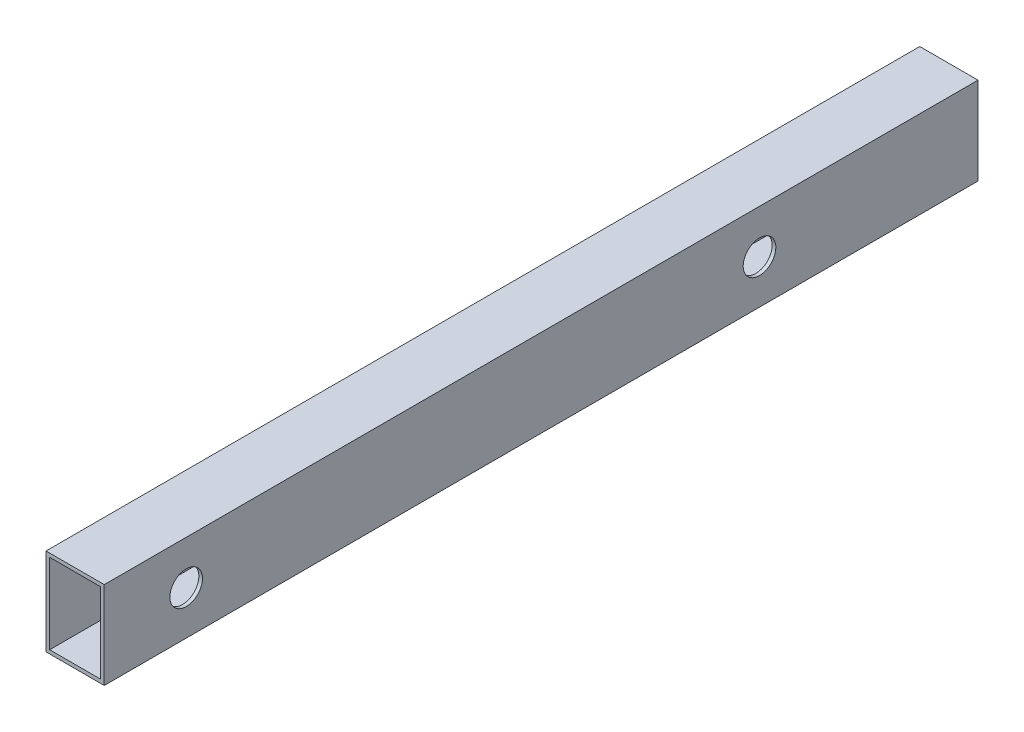
SolidWorks part; units mm, degrees
ref_plane "Front Plane" through (0, 0, 0) normal (0, 0, 1) x (1, 0, 0)
ref_plane "Top Plane" through (0, 0, 0) normal (0, 1, 0) x (1, 0, 0)
ref_plane "Right Plane" through (0, 0, 0) normal (1, 0, 0) x (0, 0, -1)
sketch "Sketch1" plane through (0, 0, 0) normal (0, 0, 1) x (1, 0, 0)
  line L0 (0, 38.1) -> (0, 34.925) construction
  line L1 (-25.4, 38.1) -> (25.4, 38.1)
  line L2 (-25.4, 38.1) -> (-25.4, -38.1)
  line L3 (-25.4, -38.1) -> (25.4, -38.1)
  line L4 (25.4, 38.1) -> (25.4, -38.1)
  line L5 (-25.4, 38.1) -> (25.4, -38.1) construction
  line L6 (-25.4, -38.1) -> (25.4, 38.1) construction
  line L7 (-22.225, 34.925) -> (22.225, 34.925)
  line L8 (-22.225, 34.925) -> (-22.225, -34.925)
  line L9 (-22.225, -34.925) -> (22.225, -34.925)
  line L10 (22.225, 34.925) -> (22.225, -34.925)
  line L11 (22.225, 0) -> (25.4, 0) construction
  line L12 (-22.225, 0) -> (-25.4, 0) construction
  line L13 (0, -34.925) -> (0, -38.1) construction
  point P0 (0, 0)
  dimension "D1" = 76.2
  dimension "D2" = 50.8
  dimension "D3" = 3.175
extrude "Boss-Extrude1" add sketch "Sketch1" along normal blind 762
sketch "Sketch2" plane through (0, 38.1, 0) normal (0, 1, 0) x (1, 0, 0)
  line L0 (-26.9875, -190.549) -> (26.9875, -190.549) construction
  line L1 (-25.4, 0) -> (25.4, 0)
  line L2 (-25.4, 0) -> (-25.4, -762)
  line L3 (-25.4, -762) -> (25.4, -762)
  line L4 (25.4, 0) -> (25.4, -762)
  line L5 (-26.4963, -703.2466) -> (26.4963, -703.2466) construction
  line L6 (0, -703.2466) -> (0, -190.549) construction
  line L7 (0, 0) -> (0, -190.549) construction
  line L8 (-74.6125, -402.6047) -> (-73.6301, -528.6965) construction
  line L9 (-74.1213, -465.6506) -> (-23.8125, -465.6506) construction
  line L10 (-23.8125, -465.6506) -> (26.9875, -465.6506) construction
  dimension "D1" = 190.549
  dimension "D2" = 512.6976
  dimension "D3" = 126.0917
  dimension "D4" = 50.3088
  dimension "D5" = 50.8
  dimension "D6" = 53.975
  dimension "D7" = 52.9926
  dimension "D8" = 275.1016
ref_plane "Plane1" through (25.4, 0, 0) normal (1, 0, 0) x (0, 0, -1)
sketch "Sketch4" plane through (25.4, 0, 0) normal (1, 0, 0) x (0, 0, -1)
  line L0 (-690.548, 38.1) -> (-690.548, 0) construction
  line L1 (-703.2466, 38.1) -> (-190.549, 38.1) construction
  line L2 (-190.549, 38.1) -> (-190.549, 0) construction
  line L3 (0, 38.1) -> (-190.549, 38.1) construction
  line L4 (-190.549, 0) -> (0, 0) construction
  line L5 (0, -38.1) -> (0, 38.1) construction
  line L6 (-190.549, 0) -> (-690.548, 0) construction
  circle A0 centre (-690.548, 0) radius 14.224
  circle A1 centre (-190.549, 0) radius 14.224
  dimension "D1" = 28.448
  dimension "D2" = 499.999
  dimension "D3" = 190.549
extrude "Cut-Extrude1" cut sketch "Sketch4" against normal up to surface (50.8 mm away) contours A1 | A0 up to face at (-25.4, 0, 381)
sketch "Sketch5" plane through (0, -38.1, 0) normal (0, -1, 0) x (1, 0, 0)
  line L0 (-25.4, 0) -> (-25.4, 762) construction
  line L2 (0, 264.16) -> (0, 328.0394) construction
  line L4 (-25.4, 264.16) -> (25.4, 264.16) construction
  line L5 (25.4, 0) -> (25.4, 762) construction
  line L6 (15.24, 264.16) -> (15.24, 340.36) construction
  line L7 (0, 703.2466) -> (0, 190.549) construction
  circle A0 centre (15.24, 264.16) radius 2.0955
  circle A1 centre (15.24, 289.56) radius 2.0955
  circle A2 centre (15.24, 314.96) radius 2.0955
  circle A3 centre (-15.24, 264.16) radius 2.0955
  circle A4 centre (-15.24, 289.56) radius 2.0955
  circle A5 centre (-15.24, 314.96) radius 2.0955
  dimension "D4" = 4.191
  dimension "D1" = 264.16
  dimension "D3" = 76.2
  dimension "D6" = 10.16
  dimension "D5" = 3
extrude "Cut-Extrude2" cut sketch "Sketch5" against normal up to surface (3.175 mm away) up to face at (0, -34.925, 381)
